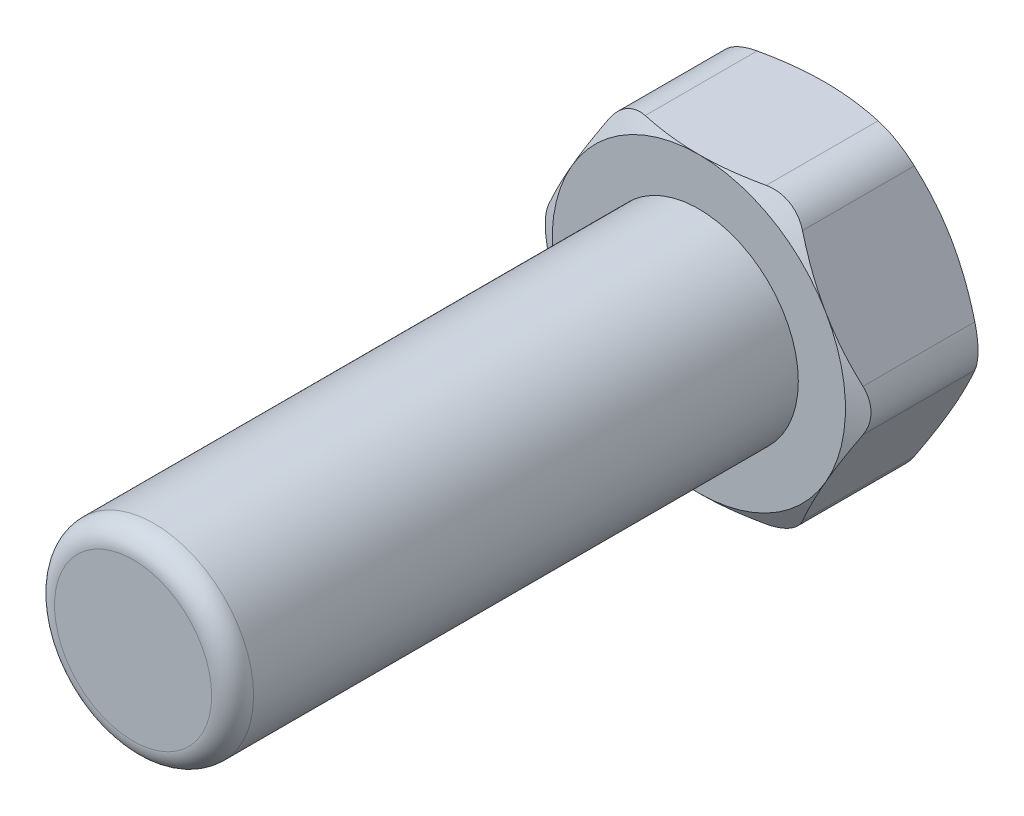
SolidWorks part; units mm, degrees
ref_plane "Front Plane" through (0, 0, 0) normal (0, 0, 1) x (1, 0, 0)
ref_plane "Top Plane" through (0, 0, 0) normal (0, 1, 0) x (1, 0, 0)
ref_plane "Right Plane" through (0, 0, 0) normal (1, 0, 0) x (0, 0, -1)
sketch "Sketch4" plane through (0, 0, 0) normal (0, 0, 1) x (1, 0, 0)
  line L1 (-2.0207, 3.5) -> (-4.0415, 0)
  line L2 (-4.0415, 0) -> (-2.0207, -3.5)
  line L3 (-2.0207, -3.5) -> (2.0207, -3.5)
  line L4 (2.0207, -3.5) -> (4.0415, 0)
  line L5 (4.0415, 0) -> (2.0207, 3.5)
  line L6 (2.0207, 3.5) -> (-2.0207, 3.5)
  circle A0 centre (0, 0) radius 3.5 construction
  circle A1 centre (0, 0) radius 2.375
  dimension "D1" = 4.75
  dimension "D2" = 7
extrude "Boss-Extrude2" add sketch "Sketch4" along normal mid plane 3 contours A1 | L5 L6 L1 L2 L3 L4 A1 region at (0, 3.3931, 0) region at (0, 0, 0)
sketch "Sketch5" plane through (0, 0, 1.5) normal (0, 0, 1) x (1, 0, 0)
  circle A0 centre (0, 0) radius 3.5 construction
  circle A1 centre (0, 0) radius 3.5
extrude "Cut-Extrude1" cut sketch "Sketch5" against normal blind 15 draft 60 flip side to cut
mirror "Mirror1" about plane through (0, 0, 0) normal (0, 0, 1) of "Cut-Extrude1"
extrude "Boss-Extrude3" add sketch "Sketch4<3>" along normal blind 15 contours A1
sketch "Sketch4<3>" plane through (0, 0, 0) normal (0, 0, 1) x (1, 0, 0) same geometry as "Sketch4"
fillet "Fillet1" radius 1 6 edges at (4.0415, 0, 0) (2.0207, -3.5, 0) (-2.0207, -3.5, 0) (-4.0415, 0, 0) (-2.0207, 3.5, 0) (2.0207, 3.5, 0)
fillet "Fillet2" radius 0.5 1 edges at (2.375, 0, 15)
